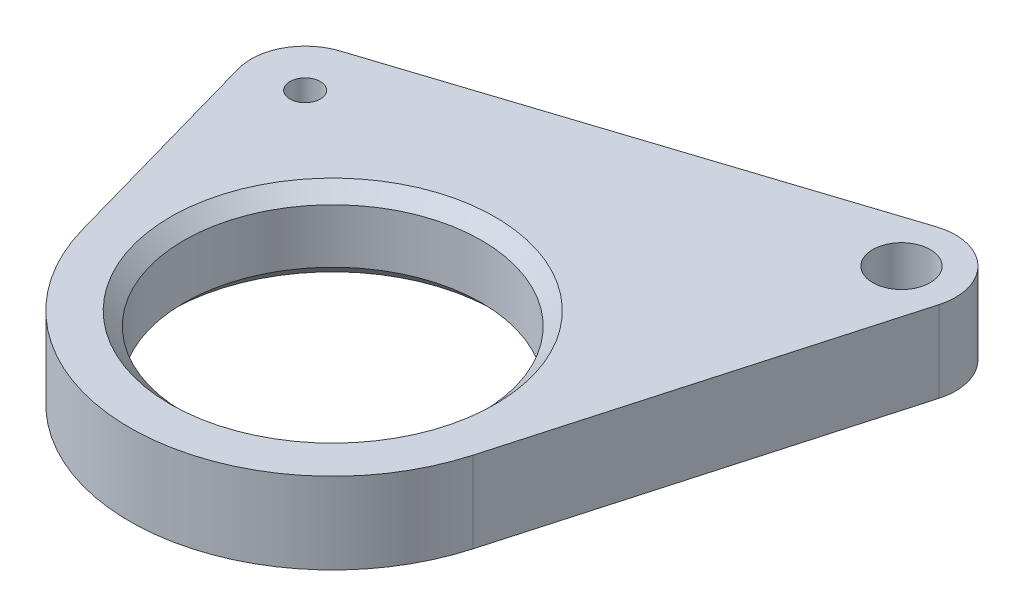
SolidWorks part; units mm, degrees
ref_plane "Front Plane" through (0, 0, 0) normal (0, 0, 1) x (1, 0, 0)
ref_plane "Top Plane" through (0, 0, 0) normal (0, 1, 0) x (1, 0, 0)
ref_plane "Right Plane" through (0, 0, 0) normal (1, 0, 0) x (0, 0, -1)
sketch "Sketch1" plane through (0, 0, 0) normal (0, 1, 0) x (1, 0, 0)
  line L0 (-14.4354, -4.0766) -> (-18.9749, 11.998)
  line L1 (-16.3581, 16.8905) -> (16.9387, 27.6759)
  line L2 (22.0207, 22.7835) -> (14.4354, -4.0766)
  line L3 (-15.1255, 13.0851) -> (0, 0) construction
  line L4 (0, 0) -> (18.1713, 23.8706) construction
  line L5 (18.1713, 23.8706) -> (-15.1255, 13.0851) construction
  circle A0 centre (0, 0) radius 11
  arc A1 (-14.4354, -4.0766) -> (14.4354, -4.0766) centre (0, 0) ccw
  arc A2 (16.9387, 27.6759) -> (22.0207, 22.7835) centre (18.1713, 23.8706) cw
  arc A3 (-18.9749, 11.998) -> (-16.3581, 16.8905) centre (-15.1255, 13.0851) cw
  circle A4 centre (-15.1255, 13.0851) radius 1.125
  circle A5 centre (18.1713, 23.8706) radius 2.125
  dimension "D1" = 22
  dimension "D2" = 15
  dimension "D3" = 4
  dimension "D4" = 20
  dimension "D6" = 2.25
  dimension "D8" = 4.25
  dimension "D5" = 35
  dimension "D7" = 30
extrude "Boss-Extrude1" add sketch "Sketch1" along normal blind 6
chamfer "Chamfer1" distance 1 angle 45 2 edges at (0, 0, 11) (0, 6, 11)
